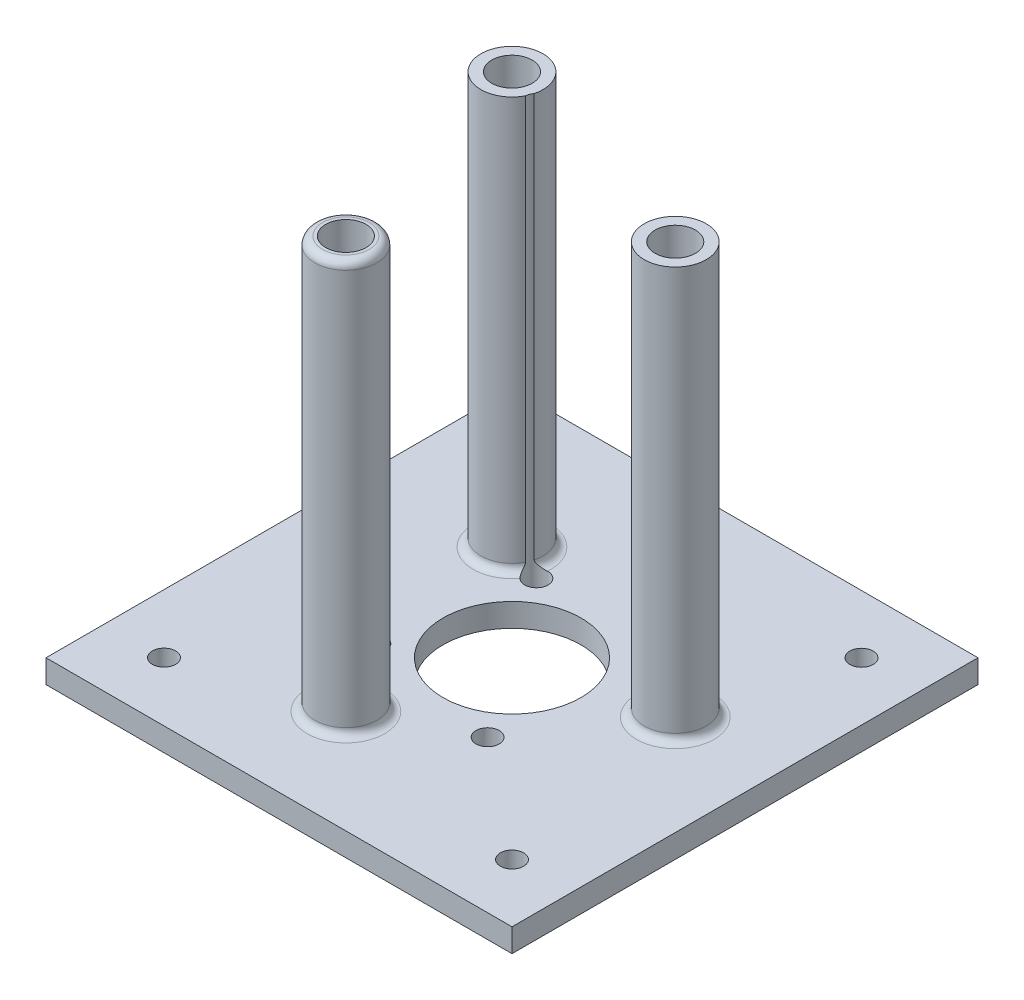
SolidWorks part; units mm, degrees
ref_plane "Front Plane" through (0, 0, 0) normal (0, 0, 1) x (1, 0, 0)
ref_plane "Top Plane" through (0, 0, 0) normal (0, 1, 0) x (1, 0, 0)
ref_plane "Right Plane" through (0, 0, 0) normal (1, 0, 0) x (0, 0, -1)
sketch "Sketch1" plane through (0, 0, 0) normal (0, 1, 0) x (1, 0, 0)
  line L0 (-0.5705, -8.9819) -> (0.4037, -8.9819)
  line L1 (-30.0834, 29.8888) -> (29.9166, 29.8888)
  line L2 (-30.0834, 29.8888) -> (-30.0834, -30.1112)
  line L3 (-30.0834, -30.1112) -> (29.9166, -30.1112)
  line L4 (29.9166, 29.8888) -> (29.9166, -30.1112)
  line L19 (-7.3758, 10.3206) -> (10.3484, 7.1812)
  line L20 (-7.3758, 10.3206) -> (-10.5151, -7.4036)
  line L21 (10.3484, 7.1812) -> (7.209, -10.5429)
  line L22 (-10.5151, -7.4036) -> (7.209, -10.5429)
  line L23 (-7.3758, 10.3206) -> (7.209, -10.5429)
  line L24 (-10.5151, -7.4036) -> (10.3484, 7.1812)
  circle A0 centre (-0.0834, -0.1112) radius 8.8841
  circle A6 centre (-10.5151, -7.4036) radius 1.5
  circle A7 centre (7.209, -10.5429) radius 1.5
  circle A8 centre (10.3484, 7.1812) radius 1.5
  circle A9 centre (-7.3758, 10.3206) radius 1.5
  point P6 (-0.0834, -0.1112)
  dimension "D9" = 3
  dimension "D10" = 3
  dimension "D11" = 3
  dimension "D12" = 3
  dimension "D1" = 60
  dimension "D2" = 60
  dimension "D3" = 30
  dimension "D4" = 30
  dimension "D5" = 18
  dimension "D6" = 18
  dimension "D7" = 0
  dimension "D8" = 0
extrude "Boss-Extrude2" add sketch "Sketch1" along normal blind 3 contours L4 L1 L2 L3 A9 L19 A8 L21 A7 L22 A6 L20 | A9 L20 A6 L24 A0 L23 | A9 L23 A0 L24 A8 L19 | A7 L23 A0 L24 A6 L22 | A8 L24 A0 L23 A7 L21 region at (-0.0834, 0, 9.1597) region at (-8.4194, 0, 5.738) region at (7.9411, 0, 4.2924) region at (-5.7102, 0, -8.2249) region at (-0.0834, 0, -29.0403)
sketch "Sketch2" plane through (0, 3, 0) normal (0, 1, 0) x (1, 0, 0)
  line L33 (-30.0834, -30.1112) -> (29.9166, -30.1112) construction
  line L34 (29.9166, 29.8888) -> (29.9166, -30.1112) construction
  line L35 (-30.0834, 29.8888) -> (29.9166, 29.8888) construction
  line L36 (-30.0834, 29.8888) -> (-30.0834, -30.1112) construction
  circle A0 centre (-22.5834, 22.3888) radius 1.5
  circle A1 centre (22.4166, 22.3888) radius 1.5
  circle A2 centre (22.4166, -22.6112) radius 1.5
  circle A4 centre (-22.5, -22.5) radius 1.5
  dimension "D9" = 7.5
  dimension "D5" = 7.5
  dimension "D6" = 7.5
  dimension "D7" = 7.5
  dimension "D8" = 7.5
  dimension "D10" = 7.5
extrude "Cut-Extrude1" cut sketch "Sketch2" against normal blind 10
sketch "Sketch3" plane through (0, 3, 0) normal (0, 1, 0) x (1, 0, 0)
  circle A0 centre (0, 0) radius 17.45
  circle A1 centre (-12.4393, 12.2379) radius 2.6
  circle A2 centre (17.0328, 3.7928) radius 2.6
  circle A3 centre (-4.8068, -16.7749) radius 2.6
  circle A4 centre (-12.4393, 12.2379) radius 4
  circle A5 centre (-4.8068, -16.7749) radius 4
  circle A6 centre (17.0328, 3.7928) radius 4
  circle M18 centre (-7.3758, 10.3206) radius 1.5
  dimension "D1" = 34.9
  dimension "D2" = 5.2
  dimension "D3" = 5.2
  dimension "D4" = 5.2
  dimension "D5" = 30
  dimension "D6" = 30
  dimension "D7" = 29.4721
  dimension "D8" = 0
  dimension "D9" = 0
extrude "Boss-Extrude3" add sketch "Sketch3" along normal blind 53 contours A0 A4 A1 | A4 A0 A1 M18 | A0 A5 A3 | A0 A5 A3 | A0 A6 A2 | A0 A6 A2 region at (17.3603, 3, 0.0922) region at (17.5351, 3, -0.6137) region at (-5.8819, 3, 20.5271) region at (-1.554, 3, 17.2904) region at (-8.7539, 3, -13.5389) region at (-9.9696, 3, -14.4444)
fillet "Fillet1" radius 1 1 edges at (-16.1801, 3, -13.6544)
fillet "Fillet2" radius 1 3 edges at (-4.8068, 3, 20.7749) (-4.8068, 56, 20.7749) (17.0328, 3, 0.2072)
